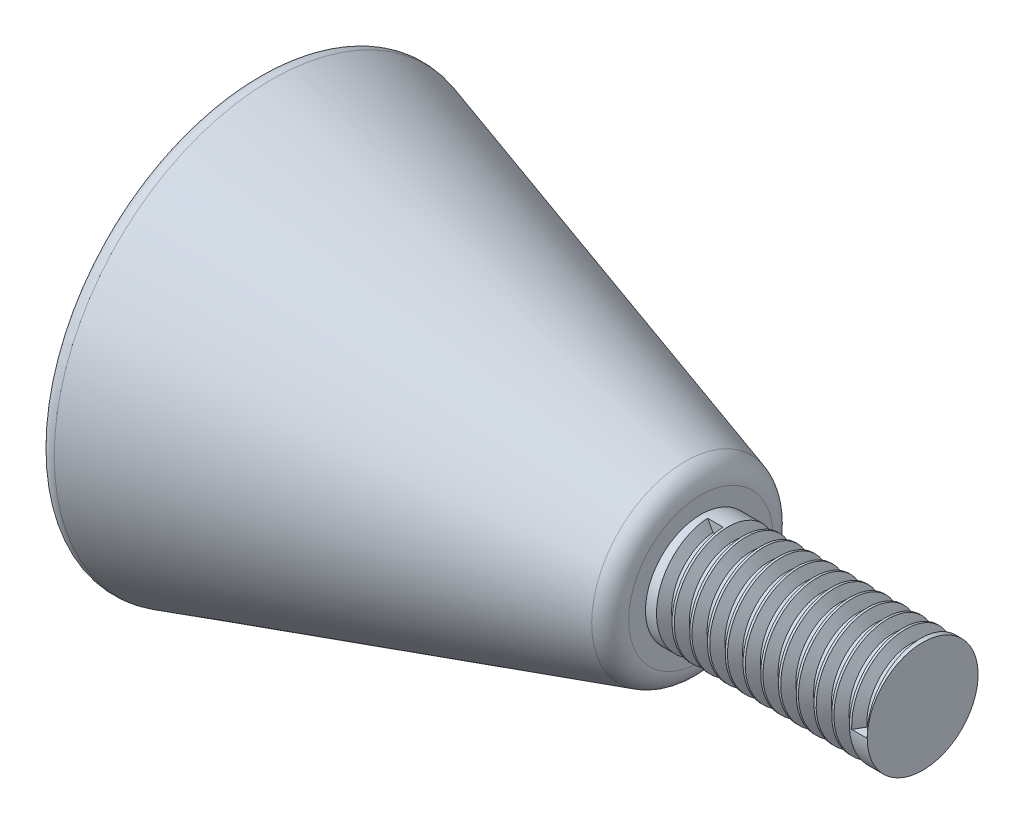
SolidWorks part; units mm, degrees
ref_plane "Front Plane" through (0, 0, 0) normal (0, 0, 1) x (1, 0, 0)
ref_plane "Top Plane" through (0, 0, 0) normal (0, 1, 0) x (1, 0, 0)
ref_plane "Right Plane" through (0, 0, 0) normal (1, 0, 0) x (0, 0, -1)
sketch "Sketch3" plane through (0, 0, 0) normal (0, 0, 1) x (1, 0, 0)
  line L0 (-52.2167, 0) -> (65.6158, 0) construction
  line L1 (-13.1034, 0) -> (-13.1034, 4)
  line L2 (-13.1034, 4) -> (-33.1034, 10)
  line L3 (-33.1034, 10) -> (-33.1034, 0)
  line L4 (-13.1034, 0) -> (-33.1034, 0)
  dimension "D1" = 10
  dimension "D2" = 4
  dimension "D3" = 20
revolve "Revolve4" add sketch "Sketch3" angle 360 about L0
fillet "Fillet1" radius 0.5 1 edges at (-33.1034, 0, 10)
fillet "Fillet2" radius 1 1 edges at (-13.1034, 0, 4)
sketch "Sketch5" plane through (-13.1034, 0, 0) normal (1, 0, 0) x (0, 0, -1)
  circle A0 centre (0, 0) radius 2.5
  dimension "D1" = 5
extrude "Boss-Extrude1" add sketch "Sketch5" along normal blind 10
thread "Thread1" pitch 0.8 method cut profile "Thread Profile1" start angle 0, offset 0, length 9, pitch 0.8, diameter 5
ref_plane "Plane1" through (-3.1034, 0, 2.5) normal (0, -1, 0) x (0, 0, 1)
sketch "Thread Profile1" plane through (-3.1034, 0, 2.5) normal (0, -1, 0) x (0, 0, 1)
  line L0 (0, 0) -> (0, 0.8) construction
  line L11 (0, 0) -> (0, 0.7)
  line L12 (0, 0.7) -> (-0.433, 0.45)
  line L13 (-0.433, 0.45) -> (-0.433, 0.25)
  line L15 (-0.433, 0.25) -> (0, 0)
  line L17 (-0.433, 0.35) -> (0, 0.35) construction
  point P2 (0, 0)
  dimension "Pitch" = 0.8
  dimension "Profile_Angle" = 60
  dimension "Profile_Land" = 0.2
  dimension "Profile_Height" = 0.433
